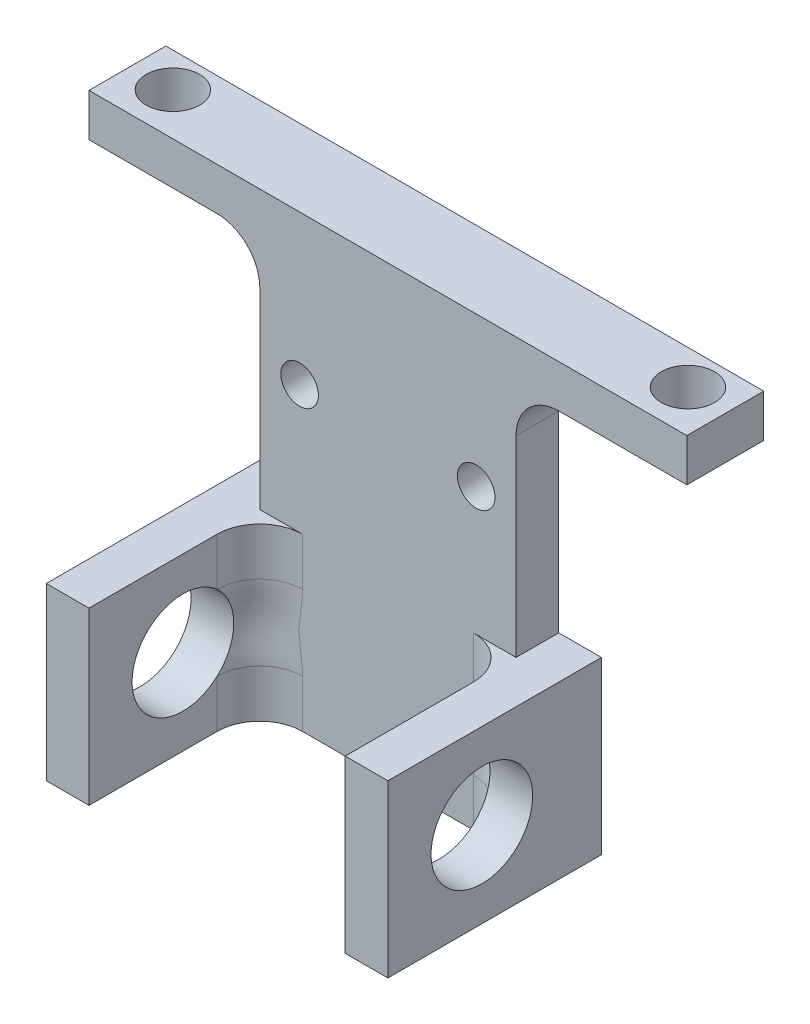
SolidWorks part; units mm, degrees
ref_plane "Front Plane" through (0, 0, 0) normal (0, 0, 1) x (1, 0, 0)
ref_plane "Top Plane" through (0, 0, 0) normal (0, 1, 0) x (1, 0, 0)
ref_plane "Right Plane" through (0, 0, 0) normal (1, 0, 0) x (0, 0, -1)
sketch "Sketch4" plane through (0, 0, 0) normal (0, 1, 0) x (1, 0, 0)
  line L1 (-17.78, 2.286) -> (17.78, 2.286)
  line L2 (-17.78, 2.286) -> (-17.78, -2.286)
  line L3 (-17.78, -2.286) -> (17.78, -2.286)
  line L4 (17.78, 2.286) -> (17.78, -2.286)
  line L5 (-17.78, 2.286) -> (17.78, -2.286) construction
  line L6 (-17.78, -2.286) -> (17.78, 2.286) construction
  point P0 (0, 0)
  dimension "D1" = 35.56
  dimension "D2" = 4.572
extrude "Boss-Extrude3" add sketch "Sketch4" along normal blind 2.54
sketch "Sketch5" plane through (0, 0, 0) normal (0, -1, 0) x (1, 0, 0)
  line L0 (0, -55) -> (0, 55) construction
  line L1 (-17.78, 2.286) -> (17.78, 2.286) construction
  circle A0 centre (-15.3162, -0.2413) radius 1.5875
  circle A1 centre (15.3162, -0.2413) radius 1.5875
  dimension "D1" = 30.6324
  dimension "D2" = 3.175
  dimension "D3" = 2.5273
sketch "Sketch7" plane through (0, -2.032, 2.286) normal (0, 0, -1) x (1, 0, 0)
  line L0 (17.78, -2.032) -> (-17.78, -2.032) construction
  line L1 (7.62, 22.098) -> (-7.62, 22.098)
  line L2 (7.62, 22.098) -> (7.62, -2.032)
  line L3 (7.62, -2.032) -> (-7.62, -2.032)
  line L4 (-7.62, 22.098) -> (-7.62, -2.032)
  line L5 (7.62, 22.098) -> (-7.62, -2.032) construction
  line L6 (7.62, -2.032) -> (-7.62, 22.098) construction
  line L8 (0, -3.429) -> (0, -0.635) construction
  point P0 (0, 10.033)
  dimension "D1" = 24.13
  dimension "D2" = 15.24
extrude "Laser PDB holes" cut sketch "Sketch5" against normal through all
extrude "Boss-Extrude5" add sketch "Sketch7" along normal blind 2.54
sketch "Sketch9" plane through (0, 0, 2.286) normal (0, 0, 1) x (1, 0, 0)
  line L1 (0, -1.397) -> (0, 1.397) construction
  line L2 (2.5146, 0) -> (-2.5146, 0) construction
  circle A0 centre (-5.2514, -6.35) radius 1.1176
  circle A1 centre (5.2514, -6.35) radius 1.1176
  dimension "D1" = 2.2352
  dimension "D2" = 6.35
  dimension "D3" = 10.5029
extrude "Cut-Extrude5" cut sketch "Sketch9" against normal through all
sketch "Sketch10" plane through (7.62, 0, 0) normal (1, 0, 0) x (0, 0, -1)
  line L1 (0.254, -24.13) -> (-12.446, -24.13)
  line L2 (0.254, -24.13) -> (0.254, -13.97)
  line L3 (0.254, -13.97) -> (-12.446, -13.97)
  line L4 (-12.446, -24.13) -> (-12.446, -13.97)
  dimension "D1" = 12.7
  dimension "D2" = 10.16
extrude "Boss-Extrude6" add sketch "Sketch10" along normal blind 2.54
mirror "Mirror1" about plane through (0, 0, 0) normal (1, 0, 0) of "Boss-Extrude6"
sketch "Sketch11" plane through (10.16, 0, 0) normal (1, 0, 0) x (0, 0, -1)
  line L0 (-12.446, -24.13) -> (0.254, -24.13) construction
  line L3 (0.254, -24.13) -> (0.254, -13.97) construction
  circle A0 centre (-6.858, -19.05) radius 3.0226
  dimension "D1" = 6.0452
  dimension "D3" = 7.112
  dimension "D2" = 5.08
extrude "Cut-Extrude6" cut sketch "Sketch11" against normal through all
fillet "Fillet1" radius 2.54 3 edges at (-7.62, 0, 1.016) (0, 0, -0.254) (7.62, 0, 1.016)
fillet "Fillet2" radius 2.54 2 edges at (7.62, -19.05, 2.286) (-7.62, -19.05, 2.286)
